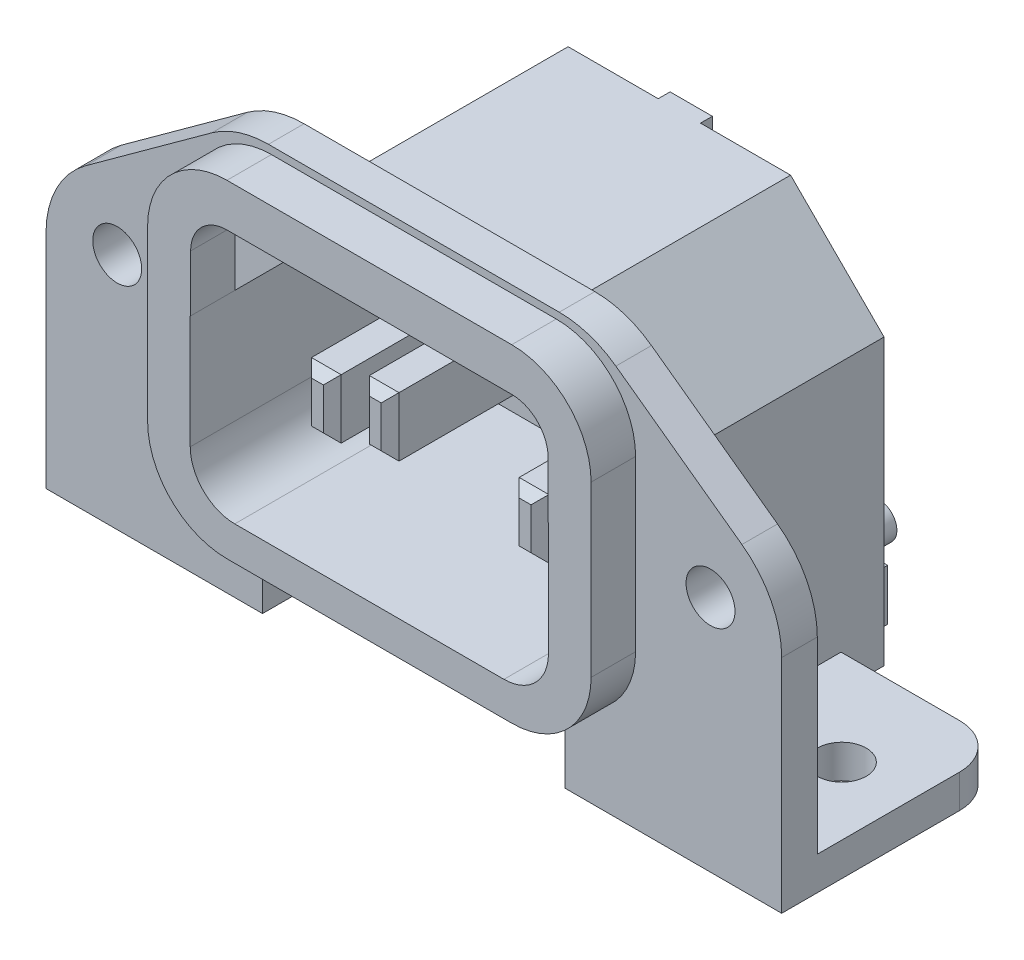
SolidWorks part; units mm, degrees
ref_plane "Front Plane" through (0, 0, 0) normal (0, 0, 1) x (1, 0, 0)
ref_plane "Top Plane" through (0, 0, 0) normal (0, 1, 0) x (1, 0, 0)
ref_plane "Right Plane" through (0, 0, 0) normal (1, 0, 0) x (0, 0, -1)
sketch "Sketch1" plane through (0, 0, 0) normal (0, 0, 1) x (1, 0, 0)
  line L0 (-22.1179, 6.3931) -> (-13.6201, 12.5605)
  line L1 (-9.8022, 13.8) -> (9.8022, 13.8)
  line L2 (-24.8, 1.1326) -> (-24.8, -13.8)
  line L3 (-24.8, -13.8) -> (-10.15, -13.8)
  line L4 (24.8, 1.1326) -> (24.8, -13.8)
  line L5 (-24.8, 13.8) -> (24.8, -13.8) construction
  line L6 (-24.8, -13.8) -> (17.5053, 9.7408) construction
  line L7 (0, 0) -> (0, 18.0303) construction
  line L8 (22.1179, 6.3931) -> (13.6201, 12.5605)
  line L9 (9.8022, 13.8) -> (24.8, 13.8) construction
  line L10 (17.5053, 9.7408) -> (24.8, 13.8) construction
  line L11 (24.8, 13.8) -> (24.8, 1.1326) construction
  line L12 (-20, 0.6) -> (-11.571, 0.6) construction
  line L13 (-21.65, 2.25) -> (-21.65, -1.1534) construction
  line L14 (-10.15, -13.8) -> (-10.15, -10.05)
  line L15 (-10.15, -10.05) -> (10.15, -10.05)
  line L16 (10.15, -10.05) -> (10.15, -13.8)
  line L17 (-10.15, -13.8) -> (10.15, -13.8) construction
  line L18 (10.15, -13.8) -> (24.8, -13.8)
  line L19 (-9.6, 13.3) -> (9.6, 13.3)
  line L20 (-9.6, 10.45) -> (9.6, 10.45) construction
  line L21 (-12.1, 7.95) -> (-12.1, -3.45) construction
  line L22 (-9.6, -5.95) -> (9.6, -5.95) construction
  line L23 (12.1, 7.95) -> (12.1, -3.45) construction
  line L24 (-12.1, 10.45) -> (12.1, -5.95) construction
  line L25 (-12.1, -5.95) -> (12.1, 10.45) construction
  line L26 (14.95, 7.95) -> (14.95, -3.45)
  line L27 (-9.6, -8.8) -> (9.6, -8.8)
  line L28 (-14.95, 7.95) -> (-14.95, -3.45)
  line L29 (-12.05, 7.95) -> (-12.05, -3.45)
  line L30 (-9.6, -5.9) -> (9.6, -5.9)
  line L31 (12.05, 7.95) -> (12.05, -3.45)
  line L32 (-9.6, 10.4) -> (9.6, 10.4)
  arc A0 (-9.8022, 13.8) -> (-13.6201, 12.5605) centre (-9.8022, 7.3) ccw
  arc A1 (-24.8, 1.1326) -> (-22.1179, 6.3931) centre (-18.3, 1.1326) cw
  arc A2 (24.8, 1.1326) -> (22.1179, 6.3931) centre (18.3, 1.1326) ccw
  arc A3 (9.8022, 13.8) -> (13.6201, 12.5605) centre (9.8022, 7.3) cw
  circle A4 centre (-20, 2.25) radius 1.65
  circle A5 centre (20, 2.25) radius 1.65
  arc A6 (-12.1, -3.45) -> (-9.6, -5.95) centre (-9.6, -3.45) ccw construction
  arc A7 (12.1, -3.45) -> (9.6, -5.95) centre (9.6, -3.45) cw construction
  arc A8 (12.1, 7.95) -> (9.6, 10.45) centre (9.6, 7.95) ccw construction
  arc A9 (-12.1, 7.95) -> (-9.6, 10.45) centre (-9.6, 7.95) cw construction
  arc A10 (14.95, 7.95) -> (9.6, 13.3) centre (9.6, 7.95) ccw
  arc A11 (14.95, -3.45) -> (9.6, -8.8) centre (9.6, -3.45) cw
  arc A12 (-14.95, -3.45) -> (-9.6, -8.8) centre (-9.6, -3.45) ccw
  arc A13 (-14.95, 7.95) -> (-9.6, 13.3) centre (-9.6, 7.95) cw
  arc A14 (-12.05, -3.45) -> (-9.6, -5.9) centre (-9.6, -3.45) ccw
  arc A15 (12.05, -3.45) -> (9.6, -5.9) centre (9.6, -3.45) cw
  arc A16 (12.05, 7.95) -> (9.6, 10.4) centre (9.6, 7.95) ccw
  arc A17 (-12.05, 7.95) -> (-9.6, 10.4) centre (-9.6, 7.95) cw
  point P0 (0, 0)
  point P32 (0, -10.05)
  point P34 (0, 2.25)
  dimension "D5" = 251.942
  dimension "D1" = 6.5
  dimension "D6" = 3.3
  dimension "D13" = 2.5
  dimension "D2" = 49.6
  dimension "D3" = 27.6
  dimension "D4" = 10.5
  dimension "D7" = 14.4
  dimension "D8" = 3.15
  dimension "D9" = 3.75
  dimension "D10" = 20.3
  dimension "D11" = 16.4
  dimension "D12" = 24.2
  dimension "D14" = 2.85
  dimension "D15" = 0.05
extrude "Boss-Extrude1" add sketch "Sketch1" along normal blind 2.4 contours A3 L1 A0 L0 A1 L2 L3 L14 L15 L16 L18 L4 A2 L8 A5 A4 L28 A13 L19 A10 L26 A11 L27 A12 | A13 L28 A12 L27 A11 L26 A10 L19 L21 A9 L20 A8 L23 A7 L22 A6 region at (-17.5356, 9.0174, 0) region at (0, 12.9282, 0)
extrude "Boss-Extrude2" add sketch "Sketch1<3>" along normal blind 3 from surface contours A13 L28 A12 L27 A11 L26 A10 L19 L21 A9 L20 A8 L23 A7 L22 A6 region at (0, 12.9282, 0) starting at face at (21.65, 2.25, 2.4)
sketch "Sketch1<3>" plane through (0, 0, 0) normal (0, 0, 1) x (1, 0, 0) same geometry as "Sketch1"
sketch "Sketch2" plane through (0, 0, 0) normal (0, 0, -1) x (-1, 0, 0)
  line L0 (24.8, -13.8) -> (10.15, -13.8) construction
  line L1 (-7.5, 11.7) -> (7.5, 11.7)
  line L2 (-13.8, 5.4) -> (-13.8, -13.8)
  line L3 (-13.8, -13.8) -> (13.8, -13.8)
  line L4 (13.8, 5.4) -> (13.8, -13.8)
  line L5 (-10.5254, 8.6746) -> (13.8, -13.8) construction
  line L6 (-13.8, -13.8) -> (10.5254, 8.6746) construction
  line L7 (-13.8, 5.4) -> (-7.5, 11.7)
  line L8 (7.5, 11.7) -> (13.8, 5.4)
  line L9 (0, -1.05) -> (0, 19.8116) construction
  line L10 (-13.8, 11.7) -> (-7.5, 11.7) construction
  line L11 (-13.8, 11.7) -> (-10.5254, 8.6746) construction
  line L12 (-13.8, 11.7) -> (-13.8, 5.4) construction
  line L13 (7.5, 11.7) -> (13.8, 11.7) construction
  line L14 (10.5254, 8.6746) -> (13.8, 11.7) construction
  line L15 (13.8, 11.7) -> (13.8, 5.4) construction
  point P0 (0, -1.05)
  dimension "D1" = 25.5
  dimension "D2" = 15
  dimension "D3" = 6.3
  dimension "D4" = 90
extrude "Boss-Extrude3" add sketch "Sketch2" along normal blind 15.5 and the other way offset from surface 3 other way up to face at (0, 2.25, 5.4)
sketch "Sketch3" plane through (0, 0, 2.4) normal (0, 0, 1) x (1, 0, 0)
  line L0 (-12.05, 7.15) -> (-8.8, 10.4)
  line L1 (0, 0) -> (0, 16.9382) construction
  line L2 (12.05, 7.15) -> (8.8, 10.4)
  arc A1 (-12.05, 7.15) -> (-8.8, 10.4) centre (-9.7647, 8.1147) cw
  arc A2 (12.05, 7.15) -> (8.8, 10.4) centre (9.7647, 8.1147) ccw
sketch "Sketch4" plane through (0, 0, -15.5) normal (0, 0, -1) x (-1, 0, 0)
  line L0 (12.075, -3.5) -> (12.075, 4.131)
  line L1 (12.075, 4.131) -> (6.206, 10)
  line L2 (6.206, 10) -> (-6.206, 10)
  line L3 (-6.206, 10) -> (-12.075, 4.131)
  line L4 (-12.075, 4.131) -> (-12.075, -3.5)
  line L5 (-9.075, -6.5) -> (9.075, -6.5)
  line L6 (13.8, -13.8) -> (13.8, 5.4)
  line L7 (13.8, 5.4) -> (7.5, 11.7)
  line L8 (7.5, 11.7) -> (-7.5, 11.7)
  line L9 (-7.5, 11.7) -> (-13.8, 5.4)
  line L10 (-13.8, 5.4) -> (-13.8, -13.8)
  line L11 (-13.8, -13.8) -> (13.8, -13.8)
  line L12 (13.8, -13.8) -> (13.8, 5.4) construction
  line L13 (13.8, 5.4) -> (7.5, 11.7) construction
  line L14 (7.5, 11.7) -> (-7.5, 11.7) construction
  line L15 (-7.5, 11.7) -> (-13.8, 5.4) construction
  line L16 (-13.8, 5.4) -> (-13.8, -13.8) construction
  line L17 (-13.8, -13.8) -> (13.8, -13.8) construction
  line L19 (0, 0) -> (0, 16.9382) construction
  arc A0 (12.075, -3.5) -> (9.075, -6.5) centre (9.075, -3.5) cw
  arc A1 (-9.075, -6.5) -> (-12.075, -3.5) centre (-9.075, -3.5) cw
  dimension "D6" = 3
  dimension "D3" = 24.15
  dimension "D2" = 16.5
  dimension "D4" = 8.3
  dimension "D5" = 270
  dimension "D1" = 0
extrude "Cut-Extrude1" cut sketch "Sketch4" against normal blind 25.5 from offset 5 offset against normal yes
extrude "Boss-Extrude4" add sketch "Sketch3" against normal up to surface (2.4 mm away) up to face at (21.65, 2.25, 0)
sketch "Sketch6" plane through (0, -13.8, 0) normal (0, -1, 0) x (1, 0, 0)
  line L0 (-24.8, 0) -> (-24.8, -9.6)
  line L1 (-21.8, -12.6) -> (-13.8, -12.6)
  line L2 (-13.8, 0) -> (-13.8, -15.5) construction
  line L3 (-24.8, 2.4) -> (24.8, 2.4) construction
  line L4 (-24.8, 0) -> (-13.8, 0)
  line L5 (-13.8, 0) -> (-13.8, -12.6)
  line L6 (-21.9, -6.2) -> (-21.9, -4.6864) construction
  line L7 (-20.25, -7.85) -> (-18.4114, -7.85) construction
  line L8 (0, 0) -> (0, -9.1869) construction
  line L9 (24.8, 0) -> (13.8, 0)
  line L10 (24.8, 0) -> (24.8, -9.6)
  line L11 (21.8, -12.6) -> (13.8, -12.6)
  line L12 (13.8, 0) -> (13.8, -12.6)
  arc A0 (-24.8, -9.6) -> (-21.8, -12.6) centre (-21.8, -9.6) ccw
  circle A1 centre (-20.25, -6.2) radius 1.65
  circle A2 centre (20.25, -6.2) radius 1.65
  arc A3 (24.8, -9.6) -> (21.8, -12.6) centre (21.8, -9.6) cw
  dimension "D1" = 15
  dimension "D2" = 3
  dimension "D3" = 2.9
  dimension "D5" = 3.3
  dimension "D4" = 4.75
extrude "Boss-Extrude5" add sketch "Sketch6" against normal blind 2.25
sketch "Sketch7" plane through (0, 0, 2.4) normal (0, 0, 1) x (1, 0, 0)
  line L0 (-10.2, -13.8) -> (-10.2, -9.8)
  line L1 (-24.8, -13.8) -> (24.8, -13.8) construction
  line L2 (-10.2, -9.8) -> (10.2, -9.8)
  line L3 (10.2, -9.8) -> (10.2, -13.8)
  line L4 (0, 0) -> (0, -4.0727) construction
  line L5 (-10.2, -13.8) -> (10.2, -13.8)
  dimension "D1" = 4
  dimension "D2" = 20.4
extrude "Cut-Extrude2" cut sketch "Sketch7" against normal blind 16
sketch "Sketch8" plane through (0, 0, -15.5) normal (0, 0, -1) x (-1, 0, 0)
  line L0 (0, 16.86) -> (0, -19.181) construction
  line L1 (-1.425, 11.7) -> (-1.425, 6.3)
  line L2 (-7.5, 11.7) -> (7.5, 11.7) construction
  line L3 (-2.6476, 3.3324) -> (-1.3, -2.2)
  line L4 (-1.3, -2.2) -> (-1.3, -10.1)
  line L5 (-13.8, -13.8) -> (13.8, -13.8) construction
  line L6 (-1.3, -10.1) -> (-0.65, -14.85)
  line L7 (-0.65, -14.85) -> (-0.65, -17.85)
  line L8 (-2.725, 3.9773) -> (2.725, 3.9773) construction
  line L9 (-0.65, -17.85) -> (0.65, -17.85)
  line L10 (-1.425, 11.7) -> (1.425, 11.7)
  line L11 (7.5, 11.7) -> (-7.5, 11.7) construction
  line L12 (0.65, -14.85) -> (0.65, -17.85)
  line L13 (-0.75, 10.2) -> (0.75, 10.2)
  line L14 (-0.75, 10.2) -> (-0.75, 7.2)
  line L15 (-0.75, 7.2) -> (0.75, 7.2)
  line L16 (0.75, 10.2) -> (0.75, 7.2)
  line L17 (-0.75, 10.2) -> (0.75, 7.2) construction
  line L18 (-0.75, 7.2) -> (0.75, 10.2) construction
  line L19 (1.3, -10.1) -> (0.65, -14.85)
  line L20 (1.3, -2.2) -> (1.3, -10.1)
  line L21 (2.6476, 3.3324) -> (1.3, -2.2)
  line L22 (1.425, 11.7) -> (1.425, 6.3)
  line L23 (-13.8, -11.55) -> (-13.8, 5.4) construction
  line L24 (4.447, -1.1452) -> (6.9, -4.55)
  line L25 (9.7, 0.55) -> (9.7, -4.55)
  line L26 (6.8, 3.45) -> (12.1154, 3.45) construction
  line L27 (6.9, -4.55) -> (6.9, -9.55)
  line L28 (9.7, -4.55) -> (9.7, -9.55)
  line L29 (6.9, -9.55) -> (8.4, -12.35)
  line L30 (8.4, -12.35) -> (8.4, -17.85)
  line L31 (9.7, -9.55) -> (9.7, -12.35)
  line L32 (9.7, -12.35) -> (9.7, -17.85)
  line L33 (8.4, -17.85) -> (9.7, -17.85)
  line L34 (-9.7, 0.55) -> (-9.7, -4.55)
  line L35 (-9.7, -4.55) -> (-9.7, -9.55)
  line L36 (-9.7, -9.55) -> (-9.7, -12.35)
  line L37 (-9.7, -12.35) -> (-9.7, -17.85)
  line L38 (-8.4, -17.85) -> (-9.7, -17.85)
  line L39 (-8.4, -12.35) -> (-8.4, -17.85)
  line L40 (-6.9, -9.55) -> (-8.4, -12.35)
  line L41 (-6.9, -4.55) -> (-6.9, -9.55)
  line L42 (-4.447, -1.1452) -> (-6.9, -4.55)
  arc A0 (-1.425, 6.3) -> (-2.6476, 3.3324) centre (0, 3.9773) ccw
  circle A1 centre (0, 3.9773) radius 1.25
  arc A2 (1.425, 6.3) -> (2.6476, 3.3324) centre (0, 3.9773) cw
  circle A3 centre (-6.8, 0.55) radius 1.25
  circle A4 centre (6.8, 0.55) radius 1.25
  arc A5 (9.7, 0.55) -> (4.447, -1.1452) centre (6.8, 0.55) ccw
  circle A6 centre (-6.8, 0.55) radius 2.9 construction
  arc A7 (4.447, -1.1452) -> (9.7, 0.55) centre (6.8, 0.55) ccw construction
  arc A8 (-9.7, 0.55) -> (-4.447, -1.1452) centre (-6.8, 0.55) cw
  point P19 (0, 8.7)
  point P28 (0, -17.85)
  point P34 (0, 11.7)
  dimension "D1" = 2.85
  dimension "D9" = 2.5
  dimension "D16" = 13.6
  dimension "D18" = 2.5
  dimension "D19" = 5.8
  dimension "D2" = 5.45
  dimension "D3" = 8.5
  dimension "D4" = 5.4
  dimension "D5" = 2.6
  dimension "D6" = 3.7
  dimension "D7" = 29.55
  dimension "D8" = 3
  dimension "D10" = 3
  dimension "D11" = 1.5
  dimension "D12" = 1.5
  dimension "D13" = 1.3
  dimension "D14" = 7.7227
  dimension "D15" = 13.8
  dimension "D17" = 11.15
  dimension "D20" = 8
  dimension "D21" = 2.8
  dimension "D22" = 5
  dimension "D23" = 2.8
  dimension "D24" = 1.3
extrude "Boss-Extrude6" add sketch "Sketch8" along normal blind 0.8
sketch "Sketch9" plane through (0, 0, -15.5) normal (0, 0, -1) x (-1, 0, 0)
  line L0 (-4.9768, 5.9229) -> (-2.9179, -2.5299)
  line L1 (-2.9179, -2.5299) -> (-2.9179, -7.6)
  line L2 (-8.4, -13.8) -> (-0.7937, -13.8) construction
  line L3 (-2.9179, -13.8) -> (-1.4179, -13.8)
  line L4 (-1.4179, -13.8) -> (-1.4179, -8.4)
  line L5 (-1.4179, -2.3499) -> (-3.5195, 6.2779)
  line L6 (-3.5195, 6.2779) -> (-4.9768, 5.9229)
  line L7 (-2.6476, 3.3324) -> (-1.3, -2.2) construction
  line L8 (0, 0) -> (0, 3.9773) construction
  line L9 (1.4179, -2.3499) -> (3.5195, 6.2779)
  line L10 (1.4179, -13.8) -> (1.4179, -8.4)
  line L11 (2.9179, -13.8) -> (1.4179, -13.8)
  line L12 (2.9179, -2.5299) -> (2.9179, -7.6)
  line L13 (4.9768, 5.9229) -> (2.9179, -2.5299)
  line L14 (3.5195, 6.2779) -> (4.9768, 5.9229)
  line L15 (0.7937, -13.8) -> (8.4, -13.8) construction
  line L16 (1.4179, -4.4057) -> (2.9179, -4.4057) construction
  line L18 (1.4179, -8.4) -> (1.4179, -7.6) construction
  line L19 (1.4179, -7.6) -> (1.4179, -2.3499)
  line L20 (2.9179, -7.6) -> (2.9179, -8.4) construction
  line L21 (2.9179, -8.4) -> (2.9179, -13.8)
  line L22 (-1.4179, -8.4) -> (-1.4179, -7.6) construction
  line L23 (-1.4179, -7.6) -> (-1.4179, -2.3499)
  line L24 (-2.9179, -7.6) -> (-2.9179, -8.4) construction
  line L25 (-2.9179, -8.4) -> (-2.9179, -13.8)
  line L28 (9.7, -17.85) -> (9.7, 0.55) construction
  line L30 (9.7, -13.8) -> (11.5, -13.8)
  line L31 (9.7, -13.8) -> (13.8, -13.8) construction
  line L32 (11.5, -13.8) -> (11.5, -10.35)
  line L33 (11.5, -10.35) -> (9.7, -10.35)
  line L34 (9.7, -10.35) -> (9.7, -13.8)
  line L35 (-11.5, -10.35) -> (-9.7, -10.35)
  line L36 (-11.5, -13.8) -> (-11.5, -10.35)
  line L37 (-9.7, -13.8) -> (-11.5, -13.8)
  line L38 (-9.7, -10.35) -> (-9.7, -13.8)
  arc A0 (2.9179, -8.4) -> (2.9179, -7.6) centre (2.1679, -8) ccw
  arc A1 (1.4179, -8.4) -> (2.9179, -8.4) centre (2.1679, -8) ccw construction
  arc A2 (2.9179, -7.6) -> (1.4179, -7.6) centre (2.1679, -8) ccw construction
  arc A3 (1.4179, -7.6) -> (1.4179, -8.4) centre (2.1679, -8) ccw
  arc A4 (-2.9179, -8.4) -> (-2.9179, -7.6) centre (-2.1679, -8) cw
  arc A5 (-1.4179, -7.6) -> (-1.4179, -8.4) centre (-2.1679, -8) cw
  circle A6 centre (5.675, -8) radius 1.2
  circle A7 centre (10.925, -8) radius 1.2
  circle A8 centre (-10.925, -8) radius 1.2
  circle A9 centre (-5.675, -8) radius 1.2
  point P46 (2.1679, -4.4057)
  dimension "D6" = 5.8
  dimension "D7" = 0.85
  dimension "D8" = 2.4
  dimension "D12" = 2.4
  dimension "D1" = 0.15
  dimension "D2" = 1.5
  dimension "D3" = 1.5
  dimension "D4" = 11.4501
  dimension "D5" = 8.7
  dimension "D9" = 1.8
  dimension "D10" = 3.45
  dimension "D11" = 5.675
  dimension "D13" = 5.25
extrude "Boss-Extrude10" add sketch "Sketch9" along normal blind 2.54
sketch "Sketch10" plane through (0, 0, -13.6) normal (0, 0, 1) x (1, 0, 0)
  line L0 (0, 0) -> (0, -20.0579) construction
  line L1 (8.6, -13.8) -> (8.6, -11.1)
  line L2 (-10.2, -13.8) -> (10.2, -13.8) construction
  line L3 (8.6, -11.1) -> (5.9, -11.1)
  line L4 (5.9, -11.1) -> (5.9, -13.8)
  line L5 (1.65, -13.8) -> (1.65, -11.1)
  line L6 (1.65, -11.1) -> (-1.65, -11.1)
  line L7 (-1.65, -11.1) -> (-1.65, -13.8)
  line L8 (10.2, -13.8) -> (10.2, -9.8) construction
  line L9 (5.9, -13.8) -> (8.6, -13.8)
  line L10 (1.65, -13.8) -> (-1.65, -13.8)
  line L11 (-5.9, -11.1) -> (-5.9, -13.8)
  line L12 (-8.6, -11.1) -> (-5.9, -11.1)
  line L13 (-8.6, -13.8) -> (-8.6, -11.1)
  line L14 (-5.9, -13.8) -> (-8.6, -13.8)
  point P11 (0, -11.1)
  dimension "D1" = 1.6
  dimension "D2" = 2.7
  dimension "D3" = 3.3
  dimension "D4" = 2.7
extrude "Cut-Extrude3" cut sketch "Sketch10" against normal up to surface (1.9 mm away) up to face at (-9.05, -15.825, -15.5)
sketch "Sketch11" plane through (0, 0, -15.5) normal (0, 0, -1) x (-1, 0, 0)
  line L0 (-12.1, -5.55) -> (-10.1973, -5.55) construction
  line L1 (0, 0) -> (0, -4.9949) construction
  line L2 (12.1, -5.55) -> (10.1973, -5.55) construction
  line L3 (-10.925, -6.8) -> (-12.9823, -6.8) construction
  line L4 (-13.8, -11.55) -> (-13.8, 5.4) construction
  circle A0 centre (-10.925, -8) radius 1.2 construction
  circle A1 centre (-10.925, -8) radius 1.2 construction
  text T0 "N" font "Century Gothic" height 2
  text T1 "L" font "Century Gothic" height 2
  dimension "D1" = 1.25
  dimension "D2" = 1.7
extrude "Boss-Extrude11" add sketch "Sketch11" along normal blind 0.1
sketch "Sketch12" plane through (0, 0, -15.5) normal (0, 0, -1) x (-1, 0, 0)
  line L0 (5.2867, 11.0846) -> (5.2867, 10.0846)
  line L1 (4.2867, 10.0846) -> (6.2867, 10.0846)
  line L2 (4.6228, 9.4846) -> (5.9505, 9.4846)
  line L3 (5.1007, 8.8846) -> (5.4726, 8.8846)
  line L4 (5.2867, 10.0846) -> (5.2867, 9.4846) construction
  line L5 (5.2867, 8.8846) -> (5.2867, 7.5846) construction
  line L6 (5.2867, 9.4846) -> (5.2867, 8.8846) construction
  point P4 (5.2867, 10.0846)
  point P12 (5.2867, 8.8846)
  point P13 (5.2867, 9.4846)
  dimension "D1" = 3.5
  dimension "D2" = 2
  dimension "D3" = 1
  dimension "D4" = 0.6
  dimension "D5" = 0.6
extrude "Extrude-Thin1" add sketch "Sketch12" along normal blind 0.1 thin thin type mid plane wall 0.25
sketch "Sketch13" plane through (0, 0, -10.5) normal (0, 0, 1) x (1, 0, 0)
  line L0 (0, 10) -> (0, -6.5) construction
  line L1 (9.075, -6.5) -> (-9.075, -6.5) construction
  line L6 (-6.206, 10) -> (6.206, 10) construction
  line L7 (8, -2.3) -> (6, -2.3)
  line L12 (-1, 5.7) -> (1, 5.7)
  line L13 (-1, 5.7) -> (-1, 1.7)
  line L14 (-1, 1.7) -> (1, 1.7)
  line L15 (1, 5.7) -> (1, 1.7)
  line L16 (-1, 5.7) -> (1, 1.7) construction
  line L17 (-1, 1.7) -> (1, 5.7) construction
  line L18 (-8, 1.7) -> (-6, 1.7)
  line L19 (-8, 1.7) -> (-8, -2.3)
  line L20 (-8, -2.3) -> (-6, -2.3)
  line L21 (-6, 1.7) -> (-6, -2.3)
  line L22 (-8, 1.7) -> (-6, -2.3) construction
  line L23 (-8, -2.3) -> (-6, 1.7) construction
  line L24 (6, 1.7) -> (6, -2.3)
  line L25 (8, 1.7) -> (8, -2.3)
  line L26 (8, 1.7) -> (6, 1.7)
  point P3 (0, 3.7)
  point P12 (-7, -0.3)
  dimension "D1" = 4
  dimension "D2" = 2
  dimension "D3" = 4.3
  dimension "D4" = 4
  dimension "D5" = 2
  dimension "D6" = 12
extrude "Boss-Extrude12" add sketch "Sketch13" along normal blind 15.5 contours L15 L12 L13 L14 region at (0, 3.7, -10.5)
extrude "Boss-Extrude13" add sketch "Sketch13<3>" along normal blind 12.4 contours L21 L18 L19 L20 | L25 L26 L24 L7 region at (7, -0.3, -10.5) region at (-7, -0.3, -10.5)
sketch "Sketch13<3>" plane through (0, 0, -10.5) normal (0, 0, 1) x (1, 0, 0) same geometry as "Sketch13"
chamfer "Chamfer1" distance 0.6 angle 45 12 edges at (7, 1.7, 1.9) (8, -0.3, 1.9) (7, -2.3, 1.9) (6, -0.3, 1.9) (-7, -2.3, 1.9) (-6, -0.3, 1.9) (-7, 1.7, 1.9) (-8, -0.3, 1.9) (0, 5.7, 5) (-1, 3.7, 5) (0, 1.7, 5) (1, 3.7, 5)
